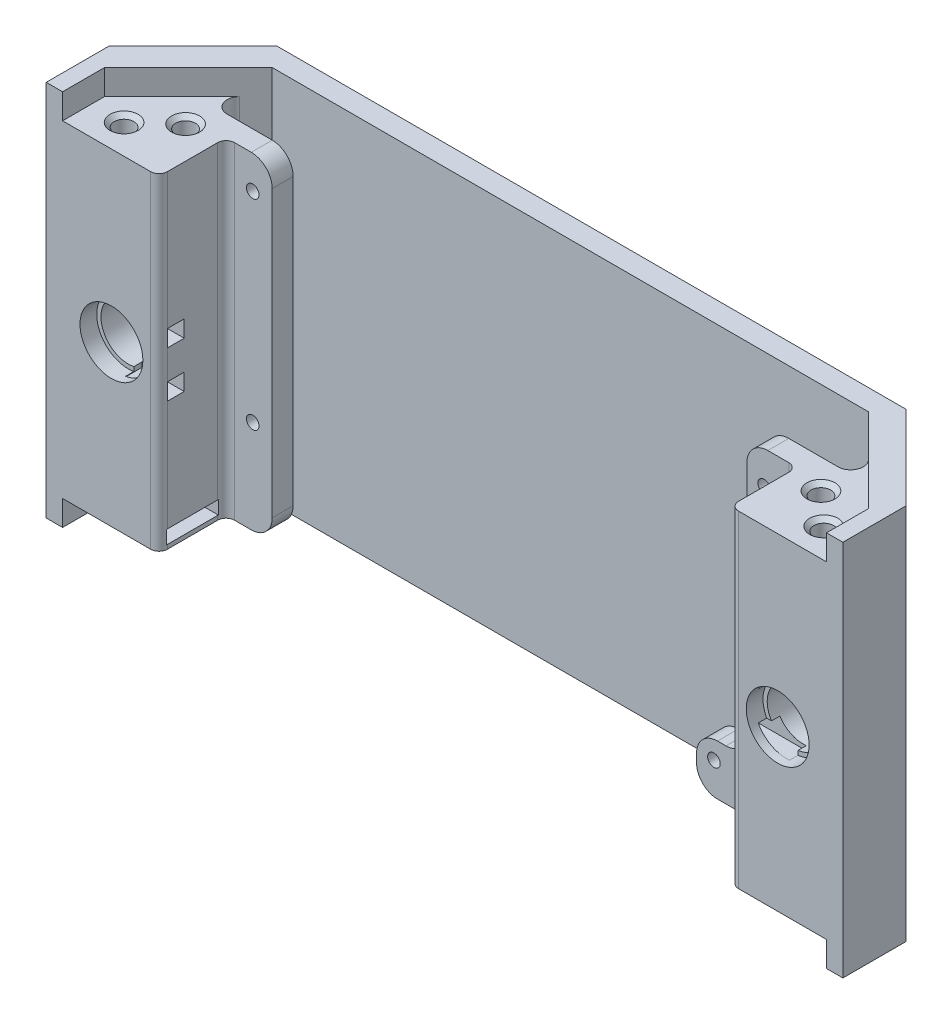
SolidWorks part; units mm, degrees
ref_plane "Front Plane" through (0, 0, 0) normal (0, 0, 1) x (1, 0, 0)
ref_plane "Top Plane" through (0, 0, 0) normal (0, 1, 0) x (1, 0, 0)
ref_plane "Right Plane" through (0, 0, 0) normal (1, 0, 0) x (0, 0, -1)
sketch "Sketch1" plane through (0, 0, 0) normal (0, 0, 1) x (1, 0, 0)
  line L1 (-95, 45) -> (95, 45)
  line L2 (-95, 45) -> (-95, -45)
  line L3 (-95, -45) -> (95, -45)
  line L4 (95, 45) -> (95, -45)
  line L5 (-95, 45) -> (95, -45) construction
  line L6 (-95, -45) -> (95, 45) construction
  point P0 (0, 0)
  point P6 (0, 0)
  dimension "D2" = 190
  dimension "D4" = 90
extrude "Boss-Extrude1" add sketch "Sketch1" along normal blind 5
sketch "Sketch2" plane through (0, 0, 5) normal (0, 0, 1) x (1, 0, 0)
  line L0 (-95, -45) -> (95, -45) construction
  line L1 (-95, 45) -> (-91.1, 45)
  line L2 (-95, 45) -> (-95, -45)
  line L3 (-95, -45) -> (-91.1, -45)
  line L4 (-91.1, 45) -> (-91.1, -45)
  line L5 (0, 0) -> (0, 45) construction
  line L6 (95, 45) -> (-95, 45) construction
  line L7 (95, -45) -> (91.1, -45)
  line L8 (91.1, 45) -> (91.1, -45)
  line L9 (95, 45) -> (91.1, 45)
  line L10 (95, 45) -> (95, -45)
  dimension "D1" = 3.9
extrude "Boss-Extrude2" add sketch "Sketch2" along normal blind 30
sketch "Sketch3" plane through (0, 45, 0) normal (0, 1, 0) x (1, 0, 0)
  line L0 (-91.1, -35) -> (-91.1, -5) construction
  line L1 (-91.1, -14) -> (-57.1, -14)
  line L2 (-91.1, -14) -> (-91.1, -19)
  line L3 (-91.1, -19) -> (-57.1, -19)
  line L4 (-57.1, -14) -> (-57.1, -19)
  line L5 (91.1, -35) -> (91.1, -5) construction
  line L6 (91.1, -14) -> (44.1, -14)
  line L7 (91.1, -14) -> (91.1, -19)
  line L8 (91.1, -19) -> (44.1, -19)
  line L9 (44.1, -14) -> (44.1, -19)
  line L10 (91.1, -5) -> (-91.1, -5) construction
  dimension "D1" = 9
  dimension "D2" = 9
  dimension "D3" = 5
  dimension "D4" = 5
  dimension "D5" = 34
  dimension "D6" = 47
extrude "Boss-Extrude3" add sketch "Sketch3" against normal up to surface (90 mm away) up to face at (0, -45, 18.75)
sketch "Sketch4" plane through (0, 0, 19) normal (0, 0, 1) x (1, 0, 0)
  line L0 (91.1, -45) -> (91.1, 45) construction
  line L1 (-91.1, 45) -> (91.1, 45)
  line L2 (-91.1, 45) -> (-91.1, 39)
  line L3 (-91.1, 39) -> (91.1, 39)
  line L4 (91.1, 45) -> (91.1, 39)
  line L5 (0, 0) -> (-91.1, 0) construction
  line L6 (-91.1, -45) -> (-91.1, 45) construction
  line L7 (-91.1, -39) -> (91.1, -39)
  line L8 (91.1, -45) -> (91.1, -39)
  line L9 (-91.1, -45) -> (91.1, -45)
  line L10 (-91.1, -45) -> (-91.1, -39)
  dimension "D1" = 6
extrude "Cut-Extrude1" cut sketch "Sketch4" against normal blind 5
sketch "Sketch5" plane through (0, 0, 19) normal (0, 0, 1) x (1, 0, 0)
  line L0 (0, 0) -> (-61.75, 0) construction
  line L1 (-70.2, 37.38) -> (70.2, 37.38) construction
  line L2 (-70.2, 37.38) -> (-70.2, -37.38) construction
  line L3 (-70.2, -37.38) -> (70.2, -37.38) construction
  line L4 (70.2, 37.38) -> (70.2, -37.38) construction
  line L5 (-70.2, 37.38) -> (70.2, -37.38) construction
  line L6 (-70.2, -37.38) -> (70.2, 37.38) construction
  line L7 (-61.75, 0) -> (-61.75, 31.13) construction
  line L8 (-61.75, 0) -> (-61.75, -16.61) construction
  line L9 (48.25, 0) -> (60.23, 0) construction
  line L10 (60.23, 0) -> (60.23, 31.13) construction
  line L11 (0, 0) -> (48.25, 0) construction
  line L12 (48.25, 0) -> (48.25, -31.38) construction
  circle A0 centre (-61.75, 31.13) radius 1.5
  circle A1 centre (-61.75, -16.61) radius 1.5
  circle A2 centre (60.23, 31.13) radius 1.5
  circle A3 centre (48.25, -31.38) radius 1.5
  point P0 (0, 0)
  dimension "D10" = 3
  dimension "D11" = 3
  dimension "D12" = 3
  dimension "D13" = 3
  dimension "D1" = 140.4
  dimension "D2" = 74.76
  dimension "D3" = 61.75
  dimension "D4" = 31.13
  dimension "D5" = 16.61
  dimension "D6" = 60.23
  dimension "D7" = 31.13
  dimension "D8" = 48.25
  dimension "D9" = 31.38
extrude "Cut-Extrude2" cut sketch "Sketch5" against normal up to surface (5 mm away) up to face at (67.6, 0, 14)
sketch "Sketch6" plane through (0, 0, 19) normal (0, 0, 1) x (1, 0, 0)
  line L1 (44.1, 39) -> (56.1, 39)
  line L2 (44.1, 39) -> (44.1, -27)
  line L3 (44.1, -27) -> (56.1, -27)
  line L4 (56.1, 39) -> (56.1, -27)
  dimension "D1" = 12
  dimension "D2" = 66
extrude "Cut-Extrude3" cut sketch "Sketch6" against normal up to surface (5 mm away) up to face at (46.75, -31.38, 14)
chamfer "Chamfer6" distance 20 angle 45 4 edges at (91.1, 0, 5) (95, 0, 0) (-95, 0, 0) (-91.1, 0, 5)
sketch "Sketch7" plane through (0, 39, 0) normal (0, 1, 0) x (1, 0, 0)
  line L0 (-85.1, -19) -> (-91.1, -25)
  line L1 (-91.1, -25) -> (-91.1, -35)
  line L2 (-91.1, -35) -> (-68.1, -35)
  line L3 (-68.1, -35) -> (-68.1, -19)
  line L4 (-85.1, -19) -> (-57.1, -19) construction
  line L5 (-68.1, -19) -> (-85.1, -19)
  line L6 (0, 0) -> (0, -5) construction
  line L7 (71.1, -5) -> (-71.1, -5) construction
  line L8 (68.1, -35) -> (68.1, -19)
  line L9 (91.1, -35) -> (68.1, -35)
  line L10 (91.1, -25) -> (91.1, -35)
  line L11 (85.1, -19) -> (91.1, -25)
  line L12 (68.1, -19) -> (85.1, -19)
  dimension "D1" = 23
extrude "Boss-Extrude4" add sketch "Sketch7" against normal up to surface (78 mm away) up to face at (-69.85, -39, 16.5)
fillet "Fillet4" radius 5 6 edges at (-57.1, -39, 16.5) (-57.1, 39, 16.5) (56.1, 39, 16.5) (44.1, -39, 16.5) (44.1, -27, 16.5) (56.1, -27, 16.5)
fillet "Fillet5" radius 2 4 edges at (-68.1, 0, 35) (68.1, 0, 35) (68.1, 0, 19) (-68.1, 0, 19)
fillet "Fillet6" radius 3 2 edges at (-80.1, 0, 14) (80.1, 0, 14)
sketch "Sketch9" plane through (0, 0, 35) normal (0, 0, 1) x (1, 0, 0)
  line L6 (0, 0) -> (0, -45) construction
  line L7 (-71.1, -45) -> (71.1, -45) construction
  line L8 (-95, 45) -> (-95, -45) construction
  line L9 (-95, 39) -> (-79.45, 39) construction
  line L10 (-95, 39) -> (-95, -0.9074) construction
  line L11 (-95, -0.9074) -> (-79.45, -0.9074) construction
  line L12 (-79.45, 39) -> (-79.45, -0.9074) construction
  line L13 (-91.1, 39) -> (-70.1, 39) construction
  circle A0 centre (-79.45, -0.9074) radius 6.5
  circle A1 centre (79.45, -0.9074) radius 6.5
  dimension "D3" = 13
  dimension "D1" = 39.9074
  dimension "D2" = 15.55
extrude "Cut-Extrude4" cut sketch "Sketch9" against normal blind 10
sketch "Sketch10" plane through (0, 0, 35) normal (0, 0, 1) x (1, 0, 0)
  circle A0 centre (-79.45, -0.9074) radius 7.5
  circle A1 centre (79.45, -0.9074) radius 7.5
  dimension "D1" = 15
  dimension "D2" = 15
extrude "Cut-Extrude5" cut sketch "Sketch10" against normal blind 4
sketch "Sketch12" plane through (-68.1, 0, 0) normal (1, 0, 0) x (0, 0, -1)
  line L0 (-33, -4.4074) -> (-29, -4.4074)
  line L1 (-33, 39) -> (-23, 39) construction
  line L2 (-33, 39) -> (-33, -0.9074) construction
  line L3 (-33, -0.9074) -> (-23, -0.9074) construction
  line L4 (-23, 39) -> (-23, -0.9074) construction
  line L5 (-33, 6.5926) -> (-23, 6.5926) construction
  line L6 (-33, 6.5926) -> (-33, -8.4074) construction
  line L7 (-33, -8.4074) -> (-23, -8.4074) construction
  line L8 (-23, 6.5926) -> (-23, -8.4074) construction
  line L9 (-33, 6.5926) -> (-23, -8.4074) construction
  line L10 (-33, -8.4074) -> (-23, 6.5926) construction
  line L11 (-33, 6.5926) -> (-29, 6.5926)
  line L12 (-33, 6.5926) -> (-33, 2.5926)
  line L13 (-33, 2.5926) -> (-29, 2.5926)
  line L14 (-29, 6.5926) -> (-29, 2.5926)
  line L15 (-29, -8.4074) -> (-29, -4.4074)
  line L16 (-33, -8.4074) -> (-29, -8.4074)
  line L17 (-33, -8.4074) -> (-33, -4.4074)
  point P5 (-28, -0.9074)
  dimension "D1" = 39.9074
  dimension "D2" = 10
  dimension "D3" = 15
  dimension "D4" = 10
  dimension "D5" = 4
  dimension "D6" = 4
extrude "Cut-Extrude6" cut sketch "Sketch12" against normal blind 10 and the other way blind 148.4
sketch "Sketch15" plane through (0, 39, 0) normal (0, 1, 0) x (1, 0, 0)
  line L0 (68.1, -21) -> (68.1, -33) construction
  line L5 (72.8574, -14) -> (61.1, -14) construction
  line L6 (91.1, -35) -> (68.1, -35) construction
  line L7 (91.1, -35) -> (91.1, -14) construction
  line L8 (91.1, -14) -> (68.1, -14) construction
  line L9 (68.1, -35) -> (68.1, -14) construction
  line L10 (68.1, -14) -> (75.7667, -21) construction
  line L11 (75.7667, -21) -> (83.4333, -28) construction
  line L12 (83.4333, -28) -> (91.1, -35) construction
  line L13 (0, 0) -> (0, -5) construction
  line L14 (71.1, -5) -> (-71.1, -5) construction
  circle A0 centre (75.7667, -21) radius 2.35
  circle A1 centre (83.4333, -28) radius 2.35
  circle A2 centre (-75.7667, -21) radius 2.35
  circle A3 centre (-83.4333, -28) radius 2.35
  dimension "D1" = 4.7
  dimension "D2" = 4.7
  dimension "D3" = 23
  dimension "D4" = 21
extrude "Cut-Extrude7" cut sketch "Sketch15" against normal blind 8
chamfer "Chamfer7" distance 1 angle 45 4 edges at (-83.4333, 39, 25.65) (-75.7667, 39, 18.65) (83.4333, 39, 30.35) (75.7667, 39, 23.35)
sketch "Sketch17" plane through (0, -39, 0) normal (0, -1, 0) x (1, 0, 0)
  line L0 (0, 0) -> (0, 5) construction
  line L1 (91.1, 35) -> (68.1, 35) construction
  line L2 (91.1, 35) -> (91.1, 19) construction
  line L3 (91.1, 19) -> (68.1, 19) construction
  line L4 (68.1, 35) -> (68.1, 19) construction
  line L5 (-71.1, 5) -> (71.1, 5) construction
  line L6 (68.1, 33) -> (68.1, 21) construction
  line L7 (66.1, 19) -> (49.1, 19) construction
  circle A0 centre (79.6, 27) radius 4
  circle A1 centre (-79.6, 27) radius 4
  dimension "D2" = 8
  dimension "D1" = 11.5
  dimension "D3" = 8
  dimension "D4" = 11.5
extrude "Cut-Extrude8" cut sketch "Sketch17" against normal blind 4.2
sketch "Sketch18" plane through (68.1, 0, 0) normal (-1, 0, 0) x (0, 0, 1)
  line L5 (27, -38) -> (27, -34.8) construction
  line L6 (33.15, -34.8) -> (20.85, -34.8)
  line L7 (33.15, -34.8) -> (33.15, -38)
  line L8 (33.15, -38) -> (20.85, -38)
  line L9 (20.85, -34.8) -> (20.85, -38)
  line L11 (27, -39) -> (27, -34.8) construction
  line L12 (33, -39) -> (21, -39) construction
  dimension "D1" = 4.2
  dimension "D2" = 12.3
  dimension "D3" = 3.2
extrude "Cut-Extrude9" cut sketch "Sketch18" against normal blind 17.6 and the other way blind 153.8
